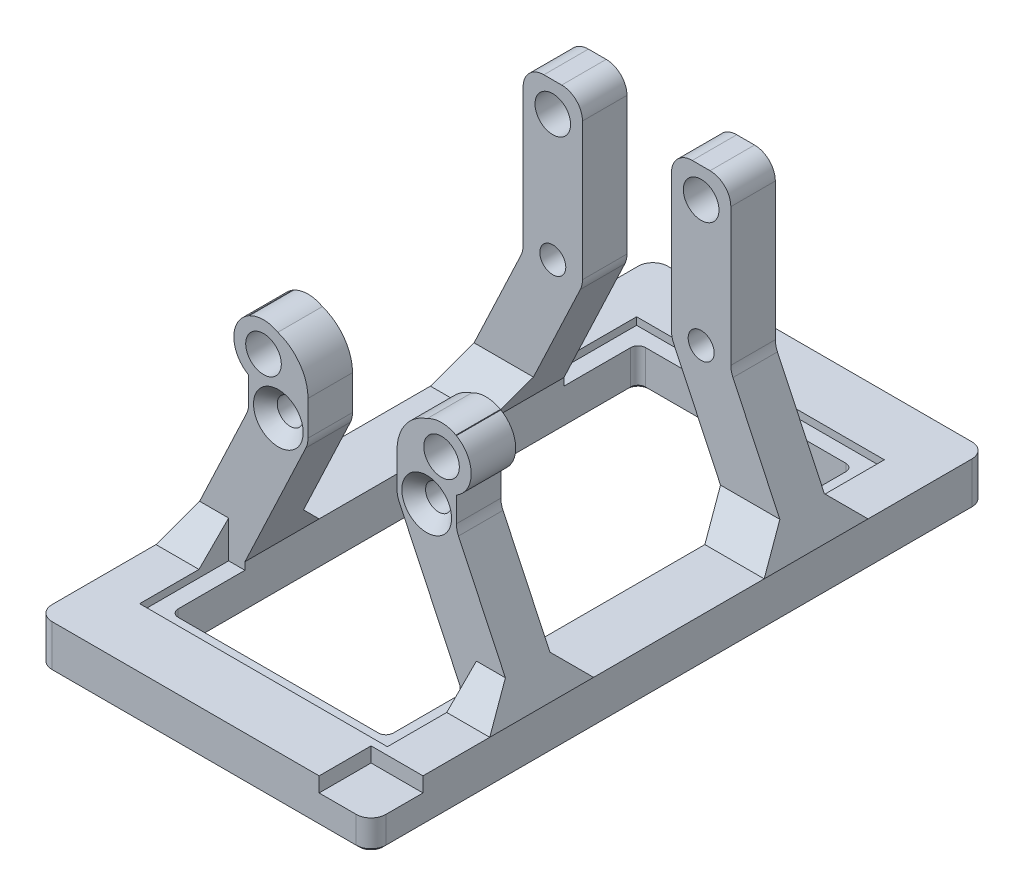
SolidWorks part; units mm, degrees
ref_plane "前视基准面" through (0, 0, 0) normal (0, 0, 1) x (1, 0, 0)
ref_plane "上视基准面" through (0, 0, 0) normal (0, 1, 0) x (1, 0, 0)
ref_plane "右视基准面" through (0, 0, 0) normal (1, 0, 0) x (0, 0, -1)
other "Configuration Table"
sketch "草图1" plane through (0, 0, 0) normal (0, 1, 0) x (1, 0, 0)
  line L0 (0, -76) -> (0, -106)
  line L1 (0, 0) -> (45, 0)
  line L2 (0, 0) -> (0, -30)
  line L3 (0, -106) -> (45, -106)
  line L4 (45, 0) -> (45, -106)
  line L5 (8, -21.5) -> (37, -21.5)
  line L6 (8, -21.5) -> (8, -37)
  line L7 (8, -84.5) -> (37, -84.5)
  line L8 (37, -21.5) -> (37, -84.5)
  line L13 (8, -69) -> (8, -84.5)
  line L18 (8, -37) -> (8, -69)
  line L19 (0, -30) -> (0, -76)
  circle A0 centre (4, -32) radius 1.75
  circle A1 centre (41, -74) radius 1.75
  dimension "D8" = 3.5
  dimension "D12" = 3.5
  dimension "D1" = 106
  dimension "D2" = 45
  dimension "D3" = 21.5
  dimension "D4" = 21.5
  dimension "D5" = 8
  dimension "D6" = 8
  dimension "D7" = 32
  dimension "D9" = 74
  dimension "D10" = 4
  dimension "D11" = 4
extrude "凸台-拉伸1" add sketch "草图1" along normal blind 6
sketch "草图3" plane through (0, 6, 0) normal (0, 1, 0) x (1, 0, 0)
  line L0 (45, -106) -> (45, 0) construction
  line L1 (0, -106) -> (45, -106)
  line L2 (0, -106) -> (0, -94.5)
  line L3 (0, -94.5) -> (45, -94.5)
  line L4 (45, -106) -> (45, -94.5)
  line L5 (37, -21.5) -> (8, -21.5) construction
  line L6 (0, 0) -> (45, 0)
  line L7 (0, 0) -> (0, -11.5)
  line L8 (0, -11.5) -> (45, -11.5)
  line L9 (45, 0) -> (45, -11.5)
  line L10 (8, -84.5) -> (37, -84.5) construction
  dimension "D1" = 10
  dimension "0" = 10
extrude "切除-拉伸1" cut sketch "草图3" against normal blind 10
sketch "草图14" plane through (0, 0, 0) normal (0, -1, 0) x (-1, 0, 0)
  circle A0 centre (-41, -74) radius 2.4
  circle A1 centre (-4, -32) radius 2.7794
  dimension "D1" = 4.8
  dimension "4.8" = 5.5589
extrude "切除-拉伸8" cut sketch "草图14" against normal blind 4.5
sketch "草图23" plane through (0, 6, 0) normal (0, 1, 0) x (1, 0, 0)
  circle A0 centre (4, -32) radius 1.75
  circle A1 centre (41, -74) radius 1.75
extrude "凸台-拉伸9" add sketch "草图23" against normal blind 0.2
ref_plane "基准面1" through (0, 0, 68.5) normal (0, 0, 1) x (1, 0, 0)
sketch "草图5" plane through (0, 0, 68.5) normal (0, 0, 1) x (1, 0, 0)
  line L0 (45, 6) -> (36.5, 24)
  line L1 (37, 6) -> (28.5, 24)
  line L2 (45, 6) -> (0, 6) construction
  line L3 (0, 6) -> (8.5, 24)
  line L4 (8, 6) -> (16.5, 24)
  line L5 (28.5, 24) -> (28.5, 35)
  line L6 (0, 6) -> (8, 6)
  line L7 (37, 6) -> (45, 6)
  line L8 (0, 0) -> (0, 6) construction
  line L15 (28.5, 35) -> (36.5, 35)
  line L17 (36.5, 24) -> (36.5, 35)
  line L19 (8.5, 24) -> (8.5, 35)
  line L20 (8.5, 35) -> (16.5, 35)
  line L22 (16.5, 24) -> (16.5, 35)
  point P1 (12.5, 35)
  point P19 (-1, 6)
  point P21 (32.5, 35)
  point P23 (26.5756, 42.6474)
  dimension "D1" = 11
  dimension "D2" = 12.5
  dimension "D3" = 0
  dimension "D4" = 29
  dimension "D5" = 20
  dimension "D6" = 8
  dimension "D7" = 8
  dimension "D8" = 11
  dimension "D9" = 11
  dimension "D10" = 8
  dimension "D11" = 0
extrude "凸台-拉伸4" add sketch "草图5" along normal blind 6 and the other way blind 37 contours L3 L6 L4 | L1 L7 L0 | L0 L1 region at (35.1379, 20.5, 68.5) region at (9.8621, 20.5, 68.5)
sketch "草图11" plane through (0, 6, 0) normal (0, 1, 0) x (1, 0, 0)
  line L1 (-8, -37.5) -> (45, -37.5)
  line L2 (-8, -37.5) -> (-8, -68.5)
  line L3 (-8, -68.5) -> (45, -68.5)
  line L4 (45, -37.5) -> (45, -68.5)
  line L5 (45, -31.5) -> (45, -74.5) construction
  line L6 (0, -74.5) -> (8, -74.5) construction
  dimension "D1" = 6
  dimension "D2" = 31
extrude "切除-拉伸6" cut sketch "草图11" along normal through all
sketch "草图7" plane through (0, 0, 74.5) normal (0, 0, 1) x (1, 0, 0)
  line L1 (45, 6) -> (0, 6) construction
  circle A2 centre (12.5, 25) radius 1.75
  circle A3 centre (32.5, 25) radius 1.75
  dimension "D1" = 3.5
  dimension "D2" = 3.5
  dimension "D3" = 19
  dimension "D4" = 19
extrude "切除-拉伸2" cut sketch "草图7" against normal through all
chamfer "倒角5" distance 4 angle 45 8 edges at (41, 6, 37.5) (41, 6, 68.5) (41, 6, 74.5) (41, 6, 31.5) (4, 6, 68.5) (4, 6, 74.5) (4, 6, 37.5) (4, 6, 31.5)
sketch "草图22" plane through (0, 6, 0) normal (0, 1, 0) x (1, 0, 0)
  line L1 (45, -94.5) -> (38, -94.5)
  line L2 (45, -94.5) -> (45, -87.5)
  line L3 (45, -87.5) -> (38, -87.5)
  line L4 (38, -94.5) -> (38, -87.5)
  dimension "D1" = 7
  dimension "D2" = 7
extrude "切除-拉伸14" cut sketch "草图22" against normal blind 2
fillet "圆角2" radius 2 4 edges at (0, 3, 11.5) (45, 3, 11.5) (45, 2, 94.5) (0, 3, 94.5)
sketch "草图19" plane through (0, 0, 74.5) normal (0, 0, 1) x (1, 0, 0)
  line L0 (8.5, 35) -> (16.5, 35) construction
  circle A0 centre (10.5, 31.5) radius 4
  circle A1 centre (12.5, 25) radius 1.75 construction
  circle A2 centre (34.5, 31.5) radius 4
  dimension "D1" = 8
  dimension "D2" = 3.5
  dimension "D3" = 2
  dimension "D4" = 2
extrude "凸台-拉伸7" add sketch "草图19" against normal up to surface (6 mm away) up to face at (10.75, 25, 68.5)
sketch "草图16" plane through (0, 0, 74.5) normal (0, 0, 1) x (1, 0, 0)
  line L0 (8.5, 35) -> (8.5635, 35) construction
  line L2 (28.5, 35) -> (32.5635, 35) construction
  circle A0 centre (10.5, 31.5) radius 2.4
  circle A1 centre (34.5, 31.5) radius 2.4
  arc A2 (8.5, 34.9641) -> (8.5, 28.0359) centre (10.5, 31.5) ccw construction
  arc A3 (36.5, 28.0359) -> (36.5, 34.9641) centre (34.5, 31.5) ccw construction
  dimension "D3" = 4.8
  dimension "D4" = 4.8
  dimension "D5" = 0
  dimension "D6" = 0
  dimension "D2" = 3.5
  dimension "D1" = 3.5
extrude "切除-拉伸10" cut sketch "草图16" against normal blind 20
sketch "草图17" plane through (0, 6, 0) normal (0, 1, 0) x (1, 0, 0)
  line L1 (5.8, -19.5) -> (39.2, -19.5)
  line L2 (5.8, -19.5) -> (5.8, -31.5)
  line L3 (5.8, -31.5) -> (39.2, -31.5)
  line L4 (39.2, -19.5) -> (39.2, -31.5)
  line L5 (5.8, -86.5) -> (39.2, -86.5)
  line L6 (5.8, -86.5) -> (5.8, -74.5)
  line L7 (5.8, -74.5) -> (39.2, -74.5)
  line L8 (39.2, -86.5) -> (39.2, -74.5)
  line L9 (37, -78.5) -> (37, -64.5) construction
  line L10 (8, -84.5) -> (37, -84.5) construction
  line L12 (37, -41.5) -> (37, -27.5) construction
  line L13 (37, -21.5) -> (8, -21.5) construction
  line L14 (0, -78.5) -> (0, -92.5) construction
  line L15 (0, -13.5) -> (0, -27.5) construction
  dimension "D1" = 5.8
  dimension "D2" = 2.2
  dimension "D3" = 2
  dimension "D4" = 12
  dimension "D5" = 5.8
  dimension "D6" = 2.2
  dimension "D7" = 2
  dimension "D8" = 12
extrude "切除-拉伸11" cut sketch "草图17" along normal through all and the other way blind 1
fillet "圆角7" radius 3 8 edges at (28.5, 24, 34.5) (28.5, 24, 71.5) (36.5, 24, 34.5) (36.5, 24, 71.5) (16.5, 24, 34.5) (16.5, 24, 71.5) (8.5, 24, 71.5) (8.5, 24, 34.5)
fillet "圆角8" radius 6 2 edges at (16.5, 35, 71.5) (28.5, 35, 71.5)
chamfer "倒角8" distance 1.6 angle 45 4 edges at (34.25, 25, 31.5) (14.25, 25, 31.5) (34.25, 25, 74.5) (14.25, 25, 74.5)
sketch "草图24" plane through (0, 35, 0) normal (0, 1, 0) x (1, 0, 0)
  line L1 (16.5, -31.5) -> (8.5, -31.5)
  line L2 (16.5, -31.5) -> (16.5, -37.5)
  line L3 (16.5, -37.5) -> (8.5, -37.5)
  line L4 (8.5, -31.5) -> (8.5, -37.5)
  line L5 (28.5, -31.5) -> (36.5, -31.5)
  line L6 (28.5, -31.5) -> (28.5, -37.5)
  line L7 (28.5, -37.5) -> (36.5, -37.5)
  line L8 (36.5, -31.5) -> (36.5, -37.5)
extrude "凸台-拉伸10" add sketch "草图24" along normal blind 11
sketch "草图21" plane through (0, 0, 31.5) normal (0, 0, -1) x (-1, 0, 0)
  line L1 (-36.5, 46) -> (-28.5, 46) construction
  circle A0 centre (-32.5, 42) radius 2.4
  circle A1 centre (-32.5, 25) radius 1.75 construction
  circle A2 centre (-12.5, 42) radius 2.4
  dimension "D1" = 4
  dimension "D2" = 0
  dimension "D4" = 4.8
  dimension "D3" = 2
extrude "切除-拉伸13" cut sketch "草图21" against normal blind 10
fillet "圆角11" radius 1 4 edges at (8, 2.5, 21.5) (8, 2.5, 84.5) (37, 2.5, 84.5) (37, 2.5, 21.5)
chamfer "倒角9" distance 1.1 angle 45 2 edges at (4, 4.5, 29.2206) (41, 4.5, 71.6)
chamfer "倒角10" distance 0.4 angle 45 18 edges at (36.7071, 0, 21.7929) (37, 0, 53) (36.7071, 0, 84.2071) (22.5, 0, 84.5) (8.2929, 0, 84.2071) (8, 0, 53) (8.2929, 0, 21.7929) (22.5, 0, 21.5) (0.5858, 0, 93.9142) (22.5, 0, 94.5) (44.4142, 0, 93.9142) (45, 0, 53) (44.4142, 0, 12.0858) (22.5, 0, 11.5) (0.5858, 0, 12.0858) (0, 0, 53) (4, 0, 29.2206) (41, 0, 71.6)
fillet "圆角12" radius 2.8 4 edges at (8.5, 46, 34.5) (16.5, 46, 34.5) (28.5, 46, 34.5) (36.5, 46, 34.5)
